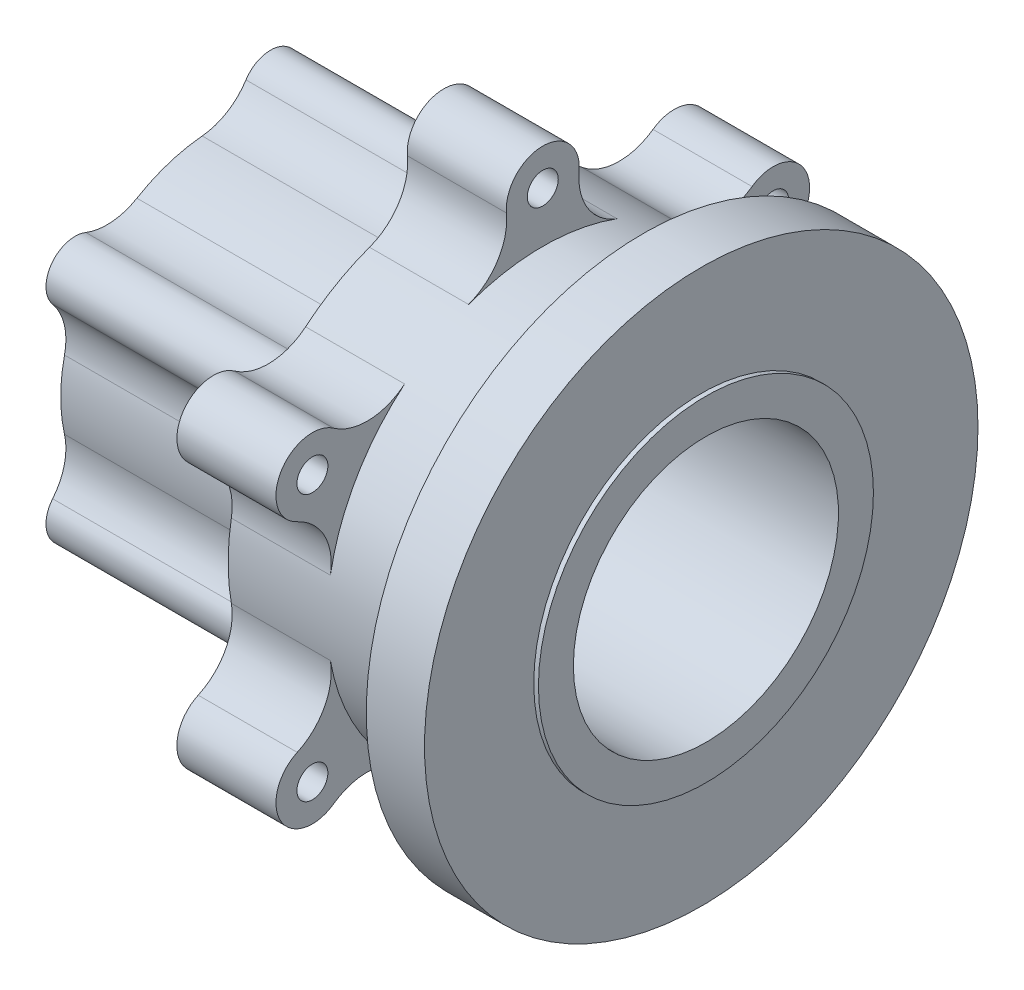
SolidWorks part; units mm, degrees
ref_plane "Front Plane" through (0, 0, 0) normal (1, 0, 0) x (0, 1, 0)
ref_plane "Top Plane" through (0, 0, 0) normal (0, 0, 1) x (0, 1, 0)
ref_plane "Right Plane" through (0, 0, 0) normal (0, 1, 0) x (-1, 0, 0)
sketch "Sketch1" plane through (0, 0, 0) normal (0, 1, 0) x (-1, 0, 0)
  line L0 (0, 68.99) -> (6.35, 68.99)
  line L1 (0, 0) -> (71.12, 0)
  line L2 (0, 0) -> (0, 157.48)
  line L3 (0, 157.48) -> (71.12, 157.48) construction
  line L4 (71.12, 0) -> (71.12, 157.48)
  line L5 (6.35, 68.99) -> (6.35, 149.987)
  line L6 (6.35, 149.987) -> (13.843, 157.48)
  line L7 (63.627, 157.48) -> (71.12, 149.987)
  line L8 (-21.844, 60.325) -> (-21.844, 36.5125)
  line L9 (0, 0) -> (-20.32, 0)
  line L10 (0, 0) -> (0, 46.99)
  line L11 (0, 46.99) -> (-20.32, 46.99)
  line L12 (-20.32, 0) -> (-20.32, 46.99)
  line L13 (71.12, 0) -> (83.82, 0) construction
  line L14 (71.12, 0) -> (71.12, 14.9987) construction
  line L15 (71.12, 14.9987) -> (83.82, 14.9987) construction
  line L16 (83.82, 0) -> (83.82, 14.9987) construction
  line L17 (83.82, 0) -> (96.52, 0) construction
  line L18 (83.82, 0) -> (83.82, 24.13) construction
  line L19 (83.82, 24.13) -> (96.52, 24.13) construction
  line L20 (96.52, 0) -> (96.52, 24.13) construction
  line L21 (-20.32, 0) -> (-35.56, 0)
  line L22 (-20.32, 0) -> (-20.32, 36.5125)
  line L23 (-20.32, 36.5125) -> (-35.56, 36.5125)
  line L24 (-35.56, 0) -> (-35.56, 36.5125)
  line L25 (-21.844, 36.5125) -> (-34.544, 36.5125)
  line L26 (-34.544, 36.5125) -> (-34.544, 60.325)
  line L27 (-34.544, 60.325) -> (-21.844, 60.325)
  line L28 (6.35, 68.99) -> (71.12, 68.99)
  dimension "D1" = 157.48
  dimension "D2" = 71.12
  dimension "D3" = 12.7
  dimension "D4" = 12.7
  dimension "D5" = 14.9987
  dimension "D6" = 24.13
  dimension "D7" = 20.32
  dimension "D8" = 45
  dimension "D9" = 45
  dimension "D10" = 6.35
  dimension "D11" = 46.99
  dimension "D13" = 36.5125
  dimension "D14" = 132.08
  dimension "D12" = 49.784
  dimension "D16" = 60.325
  dimension "D17" = 12.7
  dimension "D18" = 36.5125
  dimension "D19" = 68.99
  dimension "D15" = 1.016
revolve "Revolve1" add sketch "Sketch1" angle 360 about L1 region at (-35.56, 0, 34.495) region at (10.16, 0, 23.495) region at (27.94, 0, 18.2562)
revolve "Revolve2" add sketch "Sketch1<3>" angle 360 about L1 region at (28.194, 0, 48.4187)
sketch "Sketch1<3>" plane through (0, 0, 0) normal (0, 1, 0) x (-1, 0, 0) same geometry as "Sketch1"
sketch "Sketch2" plane through (-71.12, 0, 0) normal (-1, 0, 0) x (0, -1, 0)
  line L1 (0, -38.1) -> (36.2353, -11.7735)
  line L2 (36.2353, -11.7735) -> (22.3946, 30.8235)
  line L3 (22.3946, 30.8235) -> (-22.3946, 30.8235)
  line L4 (-22.3946, 30.8235) -> (-36.2353, -11.7735)
  line L5 (-36.2353, -11.7735) -> (0, -38.1)
  circle A0 centre (0, 0) radius 38.1
  circle A1 centre (0, 0) radius 68.99
  circle A3 centre (0, 0) radius 30.8235 construction
  circle A5 centre (0, 0) radius 68.99
  dimension "D2" = 76.2
  dimension "D1" = 0
sketch "Sketch3" plane through (-71.12, 0, 0) normal (-1, 0, 0) x (0, -1, 0)
  circle A0 centre (-22.3946, 30.8235) radius 3.3734
  circle A1 centre (22.3946, 30.8235) radius 3.3734
  circle A2 centre (36.2353, -11.7735) radius 3.3734
  circle A3 centre (0, -38.1) radius 3.3734
  circle A4 centre (-36.2353, -11.7735) radius 3.3734
  point P0 (-36.2353, -11.7735)
  point P2 (0, -38.1)
  point P4 (36.2353, -11.7735)
  point P6 (22.3946, 30.8235)
  point P8 (-22.3946, 30.8235)
  dimension "D1" = 6.7469
extrude "Cut-Extrude1" cut sketch "Sketch3" against normal blind 13.97
sketch "Sketch4" plane through (0, 0, 0) normal (1, 0, 0) x (0, 1, 0)
  line L0 (28.995, -50.2208) -> (57.99, 0)
  line L1 (57.99, 0) -> (28.995, 50.2208)
  line L2 (28.995, 50.2208) -> (-28.995, 50.2208)
  line L3 (-28.995, 50.2208) -> (-57.99, 0)
  line L4 (-57.99, 0) -> (-28.995, -50.2208)
  line L5 (-28.995, -50.2208) -> (28.995, -50.2208)
  circle A0 centre (0, 0) radius 50.2208 construction
  circle A1 centre (0, 0) radius 68.99
  circle A2 centre (0, 0) radius 68.99
  circle A3 centre (28.995, 50.2208) radius 3.3734
  dimension "D3" = 6.7469
  dimension "D2" = 115.98
  dimension "D1" = 0
sketch "Sketch5" plane through (0, 0, 0) normal (1, 0, 0) x (0, 1, 0)
  circle A0 centre (28.995, 50.2208) radius 3.3734 construction
  circle A1 centre (28.995, 50.2208) radius 3.3734
  circle A2 centre (-28.995, 50.2208) radius 3.3734
  circle A3 centre (-57.99, 0) radius 3.3734
  circle A4 centre (-28.995, -50.2208) radius 3.3734
  circle A5 centre (28.995, -50.2208) radius 3.3734
  circle A6 centre (57.99, 0) radius 3.3734
  point P0 (28.995, -50.2208)
  point P2 (57.99, 0)
  point P4 (28.995, 50.2208)
  point P9 (-28.995, -50.2208)
  point P11 (-57.99, 0)
  point P13 (-28.995, 50.2208)
extrude "Cut-Extrude2" cut sketch "Sketch5" against normal blind 13.97
sketch "Sketch10" plane through (0, 0, 0) normal (1, 0, 0) x (0, 1, 0)
  line L0 (-28.995, 50.2208) -> (0, 0) construction
  circle A0 centre (0, -38.1) radius 3.3734 construction
  circle A1 centre (-36.2353, -11.7735) radius 3.3734 construction
  circle A2 centre (-22.3946, 30.8235) radius 3.3734 construction
  circle A3 centre (36.2353, -11.7735) radius 3.3734 construction
  circle A4 centre (22.3946, 30.8235) radius 3.3734 construction
  circle A5 centre (0, -38.1) radius 3.3734
  circle A6 centre (-36.2353, -11.7735) radius 3.3734
  circle A7 centre (-22.3946, 30.8235) radius 3.3734
  circle A8 centre (36.2353, -11.7735) radius 3.3734
  circle A9 centre (22.3946, 30.8235) radius 3.3734
  circle A10 centre (57.99, 0) radius 3.3734 construction
  circle A11 centre (28.995, -50.2208) radius 3.3734 construction
  circle A12 centre (-28.995, -50.2208) radius 3.3734 construction
  circle A13 centre (-57.99, 0) radius 3.3734 construction
  circle A14 centre (-28.995, 50.2208) radius 3.3734 construction
  circle A15 centre (28.995, 50.2208) radius 3.3734 construction
  circle A16 centre (57.99, 0) radius 3.3734
  circle A17 centre (28.995, -50.2208) radius 3.3734
  circle A18 centre (-28.995, -50.2208) radius 3.3734
  circle A19 centre (-57.99, 0) radius 3.3734
  circle A20 centre (-28.995, 50.2208) radius 3.3734
  circle A21 centre (28.995, 50.2208) radius 3.3734
  circle A22 centre (0, 0) radius 68.99 construction
  circle A23 centre (0, 0) radius 46.99 construction
  circle A24 centre (0, 0) radius 68.99
  circle A25 centre (0, 0) radius 46.99
  circle A26 centre (-28.995, 50.2208) radius 7.9454
  arc A27 (-35.4699, 45.6159) -> (-36.0706, 30.1159) centre (-45.8195, 38.2554) cw
  arc A28 (-21.7696, 53.5258) -> (-8.0458, 46.2961) centre (-10.2204, 58.8085) ccw
  arc A29 (35.4699, 45.6159) -> (36.0706, 30.1159) centre (45.8195, 38.2554) ccw
  circle A30 centre (28.995, 50.2208) radius 7.9454
  arc A31 (21.7696, 53.5258) -> (8.0458, 46.2961) centre (10.2204, 58.8085) cw
  arc A32 (57.2395, -7.9099) -> (44.1165, -16.1801) centre (56.0399, -20.5531) ccw
  circle A33 centre (57.99, 0) radius 7.9454
  arc A34 (57.2395, 7.9099) -> (44.1165, 16.1801) centre (56.0399, 20.5531) cw
  arc A35 (21.7696, -53.5258) -> (8.0458, -46.2961) centre (10.2204, -58.8085) ccw
  circle A36 centre (28.995, -50.2208) radius 7.9454
  arc A37 (35.4699, -45.6159) -> (36.0706, -30.1159) centre (45.8195, -38.2554) cw
  arc A38 (-35.4699, -45.6159) -> (-36.0706, -30.1159) centre (-45.8195, -38.2554) ccw
  circle A39 centre (-28.995, -50.2208) radius 7.9454
  arc A40 (-21.7696, -53.5258) -> (-8.0458, -46.2961) centre (-10.2204, -58.8085) cw
  arc A41 (-57.2395, 7.9099) -> (-44.1165, 16.1801) centre (-56.0399, 20.5531) ccw
  circle A42 centre (-57.99, 0) radius 7.9454
  arc A43 (-57.2395, -7.9099) -> (-44.1165, -16.1801) centre (-56.0399, -20.5531) cw
  point P87 (0, 0)
  circle M12 centre (0, 0) radius 68.99
  circle M13 centre (0, 0) radius 46.99
  dimension "D1" = 4.572
  dimension "D2" = 12.7
  dimension "D3" = 6
extrude "Cut-Extrude3" cut sketch "Sketch10" against normal through all contours A43 A42 A41 A27 A26 A28 A25 A31 A30 A29 A34 A33 A32 A37 A36 A35 A40 A39 A38 M12 M13 region at (0, -67.0387, 0)
ref_plane "Plane1" through (-21.59, 0, 0) normal (1, 0, 0) x (0, 0, -1)
sketch "Sketch12" plane through (-21.59, 0, 0) normal (1, 0, 0) x (0, 0, -1)
  circle A0 centre (0, 0) radius 46.99 construction
  circle A1 centre (0, 0) radius 46.99
  circle A2 centre (0, 0) radius 65.9354
  arc A3 (-7.9099, -57.2395) -> (7.9099, -57.2395) centre (0, -57.99) ccw construction
extrude "Cut-Extrude6" cut sketch "Sketch12" against normal through all
sketch "Sketch13" plane through (-71.12, 0, 0) normal (-1, 0, 0) x (0, -1, 0)
  line L0 (0, 0) -> (0, 28.8925) construction
  line L1 (0, 0) -> (-26.1271, 35.9608) construction
  circle A0 centre (0, 0) radius 36.5125 construction
  circle A1 centre (0, 0) radius 36.5125 construction
  circle A2 centre (0, 0) radius 46.99 construction
  circle A3 centre (22.3946, 30.8235) radius 3.3734 construction
  circle A4 centre (-22.3946, 30.8235) radius 3.3734 construction
  circle A5 centre (0, 0) radius 46.99
  circle A6 centre (22.3946, 30.8235) radius 3.3734
  circle A7 centre (-22.3946, 30.8235) radius 3.3734
  circle A8 centre (0, 0) radius 28.8925
  circle A9 centre (0, 0) radius 33.9725
  circle A10 centre (-22.3946, 30.8235) radius 6.35
  arc A11 (-18.3568, 35.7244) -> (-7.4835, 33.138) centre (-10.281, 45.5261) ccw
  circle A12 centre (22.3946, 30.8235) radius 6.35
  arc A13 (18.3568, 35.7244) -> (7.4835, 33.138) centre (10.281, 45.5261) cw
  arc A14 (39.6485, -6.4189) -> (33.8287, 3.123) centre (46.4749, 4.2905) cw
  arc A15 (28.3034, 28.4978) -> (29.2036, 17.3574) centre (40.1208, 23.8462) ccw
  circle A16 centre (36.2353, -11.7735) radius 6.35
  arc A17 (6.1473, -39.6915) -> (13.4238, -31.2079) centre (18.442, -42.8744) cw
  arc A18 (35.8492, -18.1118) -> (25.5323, -22.4105) centre (35.0771, -30.7883) ccw
  circle A19 centre (0, -38.1) radius 6.35
  arc A20 (-35.8492, -18.1118) -> (-25.5323, -22.4105) centre (-35.0771, -30.7883) cw
  arc A21 (-6.1473, -39.6915) -> (-13.4238, -31.2079) centre (-18.442, -42.8744) ccw
  circle A22 centre (-36.2353, -11.7735) radius 6.35
  arc A23 (-28.3034, 28.4978) -> (-29.2036, 17.3574) centre (-40.1208, 23.8462) cw
  arc A24 (-39.6485, -6.4189) -> (-33.8287, 3.123) centre (-46.4749, 4.2905) ccw
  circle A25 centre (-22.3946, 30.8235) radius 6.35
  point P57 (0, 0)
  circle M8 centre (0, 0) radius 46.99
  dimension "D1" = 7.62
  dimension "D2" = 5.08
  dimension "D3" = 44.45
  dimension "D4" = 12.7
  dimension "D5" = 5
extrude "Cut-Extrude7" cut sketch "Sketch13" against normal up to surface (49.53 mm away) contours A22 A24 A9 A23 A10 A11 A13 A12 A15 A14 A16 A18 A17 A19 A21 A20 M8 region at (-71.12, 45.6609, 0) up to face at (-21.59, 26.4329, 45.783)
extrude "Cut-Extrude8" cut sketch "Sketch13<3>" against normal through all contours A8 region at (-71.12, 0, 0)
sketch "Sketch13<3>" plane through (-71.12, 0, 0) normal (-1, 0, 0) x (0, -1, 0) same geometry as "Sketch13"
equation "\"D9@Sketch1\"=\"D8@Sketch1\""
equation "\"D19@Sketch1\"=115.98mm-\"D11@Sketch1\""
